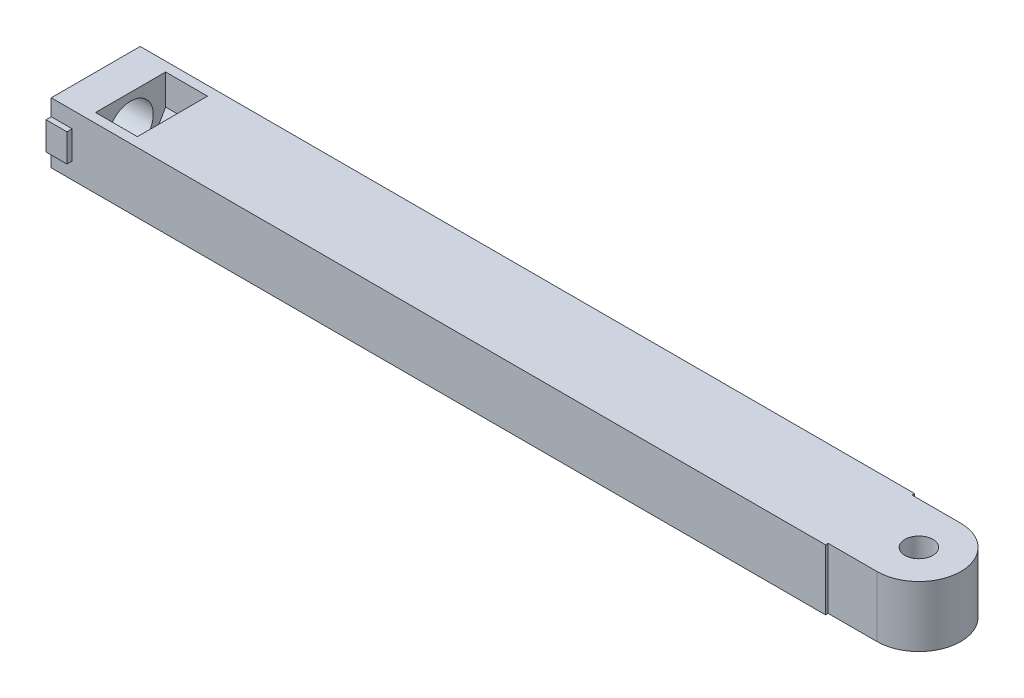
SolidWorks part; units mm, degrees
ref_plane "Front Plane" through (0, 0, 0) normal (0, 0, 1) x (1, 0, 0)
ref_plane "Top Plane" through (0, 0, 0) normal (0, 1, 0) x (1, 0, 0)
ref_plane "Right Plane" through (0, 0, 0) normal (1, 0, 0) x (0, 0, -1)
sketch "Sketch3" plane through (0, 0, 0) normal (0, 1, 0) x (1, 0, 0)
  line L0 (0, 6) -> (-7, 6)
  line L1 (-7, 6) -> (-7, -6)
  line L2 (-7, -6) -> (0, -6)
  arc A0 (0, 6) -> (0, -6) centre (0, 0) cw
  circle A1 centre (0, 0) radius 2
  dimension "D1" = 4
  dimension "D2" = 6
  dimension "D3" = 7
extrude "Boss-Extrude1" add sketch "Sketch3" along normal blind 4.35 and the other way blind 4.35
sketch "Sketch4" plane through (-7, 0, 0) normal (-1, 0, 0) x (0, 0, 1)
  line L1 (-6.375, -4.35) -> (6.375, -4.35)
  line L2 (-6.375, -4.35) -> (-6.375, -0.75)
  line L3 (-6.375, 4.35) -> (6.375, 4.35)
  line L4 (6.375, -4.35) -> (6.375, 0.8179)
  line L5 (-6.375, -4.35) -> (6.375, 4.35) construction
  line L6 (-6.375, 4.35) -> (6.375, -4.35) construction
  line L12 (-6.375, -0.75) -> (-6.375, 4.35)
  line L13 (6.375, 0.8179) -> (6.375, 4.35)
  point P0 (0, 0)
  dimension "D1" = 8.7
  dimension "D2" = 12.75
extrude "Boss-Extrude2" add sketch "Sketch4" along normal blind 111
sketch "Sketch5" plane through (-118, 0, 0) normal (-1, 0, 0) x (0, 0, 1)
  circle A0 centre (0, 0) radius 3.25
  dimension "D1" = 6.5
extrude "Cut-Extrude1" cut sketch "Sketch5" against normal blind 113
sketch "Sketch6" plane through (-118, 0, 0) normal (-1, 0, 0) x (0, 0, 1)
  line L0 (-5.025, 0) -> (-5.025, 4.3518)
  line L1 (-2.5125, 4.3518) -> (-5.025, 0) construction
  line L2 (-5.025, 0) -> (-2.5125, -4.3518)
  line L3 (-2.5125, -4.3518) -> (2.5125, -4.3518)
  line L4 (2.5125, -4.3518) -> (5.025, 0)
  line L5 (5.025, 0) -> (2.5125, 4.3518) construction
  line L6 (2.5125, 4.3518) -> (-2.5125, 4.3518)
  line L7 (-5.025, 4.3518) -> (-2.5125, 4.3518)
  line L8 (2.5125, 4.3518) -> (5.025, 4.3518)
  line L9 (5.025, 4.3518) -> (5.025, 0)
  circle A0 centre (0, 0) radius 4.3518 construction
  dimension "D1" = 10.05
extrude "Cut-Extrude2" cut sketch "Sketch6" against normal blind 6 from offset 5 offset against normal yes
sketch "Sketch8" plane through (-118, 0, 0) normal (-1, 0, 0) x (0, 0, 1)
  line L0 (-6.375, 4.35) -> (-6.375, -4.35) construction
  line L1 (-6.375, 2) -> (-7.125, 2)
  line L2 (-6.375, 2) -> (-6.375, -2)
  line L3 (-6.375, -2) -> (-7.125, -2)
  line L4 (-7.125, 2) -> (-7.125, -2)
  line L5 (6.375, -4.35) -> (6.375, 4.35) construction
  line L6 (6.375, 2) -> (7.125, 2)
  line L7 (6.375, 2) -> (6.375, -2)
  line L8 (6.375, -2) -> (7.125, -2)
  line L9 (7.125, 2) -> (7.125, -2)
  point P12 (-6.375, 0)
  point P13 (6.375, 0)
  dimension "D1" = 0.75
  dimension "D2" = 0.75
  dimension "D3" = 4
  dimension "D4" = 4
extrude "Boss-Extrude4" add sketch "Sketch8" against normal blind 3
